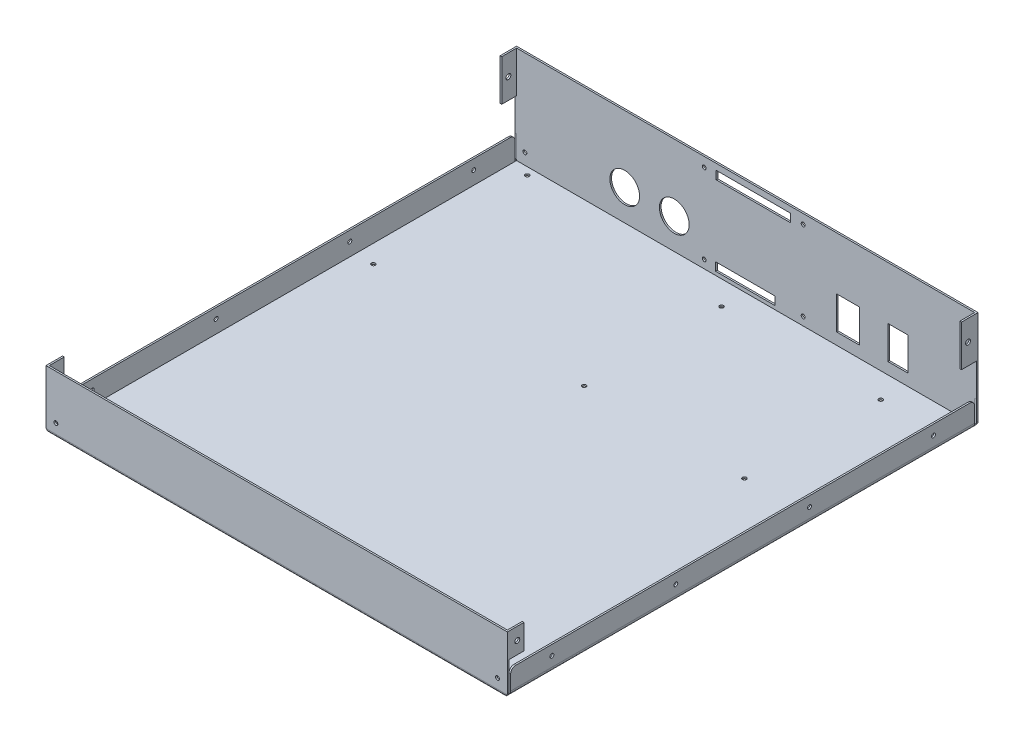
SolidWorks part; units mm, degrees
material "AISI 1015 Steel, Cold Drawn (SS)"
ref_plane "Front Plane" through (0, 0, 0) normal (0, 0, 1) x (1, 0, 0)
ref_plane "Top Plane" through (0, 0, 0) normal (0, 1, 0) x (1, 0, 0)
ref_plane "Right Plane" through (0, 0, 0) normal (1, 0, 0) x (0, 0, -1)
sketch "Sketch6" plane through (0, 0, 0) normal (0, 1, 0) x (1, 0, 0)
  line L1 (0, -162.3156) -> (279.4, -162.3156)
  line L2 (0, -162.3156) -> (0, 122.6844)
  line L3 (0, 122.6844) -> (279.4, 122.6844)
  line L4 (279.4, -162.3156) -> (279.4, 122.6844)
  dimension "D1" = 285
  dimension "D2" = 279.4
extrude "Boss-Extrude2" add sketch "Sketch6" along normal blind 60
sketch "Sketch8" plane through (0, 0, 0) normal (1, 0, 0) x (0, 0, -1)
  line L0 (-162.3156, 35) -> (-161.3156, 35)
  line L1 (-162.3156, 60) -> (-162.3156, 0) construction
  line L2 (-161.3156, 35) -> (-161.3156, 15)
  line L3 (-161.3156, 15) -> (121.6844, 15)
  line L4 (121.6844, 15) -> (121.6844, 60)
  line L5 (-162.3156, 60) -> (122.6844, 60) construction
  line L6 (121.6844, 60) -> (-162.3156, 60)
  line L7 (-162.3156, 60) -> (-162.3156, 35)
  line L8 (122.6844, 60) -> (122.6844, 0) construction
  line L9 (-162.3156, 0) -> (122.6844, 0) construction
  dimension "D1" = 1
  dimension "D2" = 1
  dimension "D3" = 15
  dimension "D4" = 35
extrude "Cut-Extrude7" cut sketch "Sketch8" against normal blind 60 and the other way through all from offset 30
shell "Shell1" thickness 1 removed face at (139.7, 15, 19.8156)
sketch "Sketch9" plane through (0, 0, -122.6844) normal (0, 0, -1) x (-1, 0, 0)
  line L0 (-279.4, 60) -> (0, 60) construction
  line L1 (-279.4, 60) -> (-279.4, 0) construction
  line L2 (-279.4, 0) -> (0, 0) construction
  line L3 (0, 60) -> (0, 0) construction
  line L4 (-279.4, 60) -> (0, 60)
  line L5 (-279.4, 60) -> (-279.4, 3)
  line L6 (-276.4, 0) -> (-3, 0)
  line L7 (0, 60) -> (0, 3)
  arc A0 (-276.4, 0) -> (-279.4, 3) centre (-276.4, 3) cw
  arc A1 (-3, 0) -> (0, 3) centre (-3, 3) ccw
  dimension "D1" = 3
extrude "Cut-Extrude8" cut sketch "Sketch9" against normal through all flip side to cut
sketch "Sketch11" plane through (279.4, 0, 0) normal (1, 0, 0) x (0, 0, -1)
  line L0 (-162.3156, 0) -> (122.6844, 0) construction
  line L1 (-161.3156, 15) -> (-157.3156, 15)
  line L2 (-161.3156, 15) -> (-161.3156, 1.9)
  line L3 (-160.4156, 1) -> (-160.3156, 1)
  line L4 (-160.3156, 12) -> (-160.3156, 1)
  line L6 (121.6836, 15.0003) -> (117.6836, 15.0003)
  line L7 (121.6836, 15.0003) -> (121.6836, 1.9)
  line L8 (120.7836, 1) -> (120.6836, 1)
  line L9 (120.6836, 12.0003) -> (120.6836, 1)
  arc A0 (120.7836, 1) -> (121.6836, 1.9) centre (120.7836, 1.9) ccw
  arc A1 (-161.3156, 1.9) -> (-160.4156, 1) centre (-160.4156, 1.9) ccw
  arc A2 (120.6836, 12.0003) -> (117.6836, 15.0003) centre (117.6836, 12.0003) ccw
  arc A3 (-160.3156, 12) -> (-157.3156, 15) centre (-157.3156, 12) cw
  dimension "D5" = 0.9
  dimension "D6" = 0.9
  dimension "D3" = 3
  dimension "D2" = 1
  dimension "D4" = 1
extrude "Cut-Extrude11" cut sketch "Sketch11" against normal through all
fillet "Fillet2" radius 2 2 edges at (139.7, 0, -122.6844) (139.7, 0, 162.3156) tangent propagation no
sketch "Sketch13" plane through (279.4, 0, 0) normal (1, 0, 0) x (0, 0, -1)
  line L0 (-157.3156, 15) -> (117.7237, 15) construction
  line L1 (-19.816, 3) -> (-19.816, 69.1905) construction
  line L2 (-160.3156, 3) -> (120.6836, 3) construction
  line L3 (-160.3156, 9) -> (141.1101, 9) construction
  line L4 (-160.3156, 3) -> (-160.3156, 12) construction
  circle A0 centre (-135.3156, 9) radius 1.5
  circle A1 centre (-60.3156, 9) radius 1.5
  circle A2 centre (20.6836, 9) radius 1.5
  circle A3 centre (95.6836, 9) radius 1.5
  dimension "D1" = 3
  dimension "D3" = 25
  dimension "D2" = 6
  dimension "D4" = 2
sketch "Sketch14" plane through (279.4, 0, 0) normal (1, 0, 0) x (0, 0, -1)
  line L0 (-162.3156, 35) -> (-162.3156, 3) construction
  line L1 (-162.3156, 35) -> (-152.3156, 35)
  line L2 (-162.3156, 35) -> (-162.3156, 20)
  line L3 (-162.3156, 20) -> (-152.3156, 20)
  line L4 (-152.3156, 35) -> (-152.3156, 20)
  line L5 (122.6844, 60) -> (112.6844, 60)
  line L6 (122.6844, 60) -> (122.6844, 35)
  line L7 (122.6844, 35) -> (112.6844, 35)
  line L8 (112.6844, 60) -> (112.6844, 35)
  line L9 (-162.3156, 35) -> (-161.3156, 35) construction
  dimension "D1" = 10
  dimension "D2" = 25
  dimension "D3" = 10
  dimension "D4" = 15
extrude "Boss-Extrude3" add sketch "Sketch14" against normal blind 1
sketch "Sketch15" plane through (0, 0, 0) normal (-1, 0, 0) x (0, 0, 1)
  line L1 (152.3156, 35) -> (162.3156, 35)
  line L2 (152.3156, 35) -> (152.3156, 20)
  line L3 (152.3156, 20) -> (162.3156, 20)
  line L4 (162.3156, 35) -> (162.3156, 20)
  line L5 (-112.6844, 60) -> (-122.6844, 60)
  line L6 (-112.6844, 60) -> (-112.6844, 35)
  line L7 (-112.6844, 35) -> (-122.6844, 35)
  line L8 (-122.6844, 60) -> (-122.6844, 35)
  dimension "D1" = 10
  dimension "D2" = 25
  dimension "D3" = 10
  dimension "D4" = 15
extrude "Boss-Extrude4" add sketch "Sketch15" against normal blind 1
sketch "Sketch16" plane through (0, 0, 0) normal (-1, 0, 0) x (0, 0, 1)
  line L0 (162.3156, 35) -> (162.3156, 3) construction
  line L1 (-122.6844, 60) -> (-122.6844, 3) construction
  circle A0 centre (156.3156, 27.5) radius 1.5
  circle A1 centre (-116.6844, 47.5) radius 1.5
  dimension "D1" = 6
  dimension "D2" = 6
extrude "Cut-Extrude14" cut sketch "Sketch16" against normal through all
hole_wizard "3/32 (0.09375) Diameter Hole2" positions "Sketch21" profile "Sketch20" hole size "3/32" standard "ANSI Inch"
sketch "Sketch21" plane through (0, 0, 162.3156) normal (0, 0, 1) x (1, 0, 0)
  point P0 (6, 7.825)
  point P3 (273.4, 7.825)
sketch "Sketch20" plane through (6, 7.825, 162.3156) normal (1, 0, 0) x (0, -1, 0)
  line L0 (0, 0) -> (0, 12.6554)
  line L1 (0, 12.6554) -> (1.1906, 11.94)
  line L2 (1.1906, 11.94) -> (1.1906, 0)
  line L5 (1.1906, 0) -> (0, 0)
  line L10 (0, 12.6554) -> (-1.1906, 11.94) construction
  line L11 (0, -6.35) -> (0, 107.95) construction
  dimension "Hole Dia." = 2.3812
  dimension "Hole Depth" = 11.94
  dimension "Drill Angle" = 118
hole_wizard "3/32 (0.09375) Diameter Hole3" positions "Sketch23" profile "Sketch22" hole size "3/32" standard "ANSI Inch"
sketch "Sketch23" plane through (0, 0, -122.6844) normal (0, 0, -1) x (-1, 0, 0)
  point P0 (-6, 7.825)
  point P3 (-273.4, 7.825)
sketch "Sketch22" plane through (6, 7.825, -122.6844) normal (1, 0, 0) x (0, 1, 0)
  line L0 (0, 0) -> (0, 12.6554)
  line L1 (0, 12.6554) -> (1.1906, 11.94)
  line L2 (1.1906, 11.94) -> (1.1906, 0)
  line L5 (1.1906, 0) -> (0, 0)
  line L10 (0, 12.6554) -> (-1.1906, 11.94) construction
  line L11 (0, -6.35) -> (0, 107.95) construction
  dimension "Hole Dia." = 2.3812
  dimension "Hole Depth" = 11.94
  dimension "Drill Angle" = 118
sketch "Sketch36" plane through (0, 0, -122.6844) normal (0, 0, -1) x (-1, 0, 0)
  line L0 (-279.4, 60) -> (-279.4, 3) construction
  line L1 (-194.6663, 8) -> (-208.6663, 8)
  line L2 (-194.6663, 8) -> (-194.6663, 28)
  line L3 (-194.6663, 28) -> (-208.6663, 28)
  line L4 (-208.6663, 8) -> (-208.6663, 28)
  line L5 (-279.2284, 2) -> (-0.1716, 2) construction
  line L6 (-237.9, 28) -> (-225.9, 28)
  line L7 (-237.9, 28) -> (-237.9, 8)
  line L8 (-237.9, 8) -> (-225.9, 8)
  line L9 (-225.9, 28) -> (-225.9, 8)
  line L11 (-166.8765, 51.3214) -> (-121.8765, 51.3214)
  line L12 (-166.8765, 51.3214) -> (-166.8765, 56.3214)
  line L13 (-166.8765, 56.3214) -> (-121.8765, 56.3214)
  line L14 (-121.8765, 51.3214) -> (-121.8765, 56.3214)
  line L15 (-166.8765, 51.3214) -> (-121.8765, 56.3214) construction
  line L16 (-166.8765, 56.3214) -> (-121.8765, 51.3214) construction
  line L17 (-157.5724, 3.1942) -> (-121.5724, 3.1942)
  line L18 (-157.5724, 3.1942) -> (-157.5724, 8.1942)
  line L19 (-157.5724, 8.1942) -> (-121.5724, 8.1942)
  line L20 (-121.5724, 3.1942) -> (-121.5724, 8.1942)
  line L21 (-157.5724, 3.1942) -> (-121.5724, 8.1942) construction
  line L22 (-157.5724, 8.1942) -> (-121.5724, 3.1942) construction
  circle A0 centre (-96.4719, 19.6) radius 9
  circle A1 centre (-66.4719, 19.6) radius 9
  point P12 (-144.3765, 53.8214)
  point P17 (-139.5724, 5.6942)
  dimension "D13" = 18
  dimension "D14" = 18
  dimension "D1" = 14
  dimension "D2" = 20
  dimension "D3" = 12
  dimension "D4" = 20
  dimension "D5" = 6
  dimension "D6" = 6
  dimension "D7" = 17.2337
  dimension "D8" = 41.5
  dimension "D9" = 5
  dimension "D10" = 5
  dimension "D11" = 45
  dimension "D12" = 36
extrude "Cut-Extrude15" cut sketch "Sketch36" against normal blind 2
hole_wizard "3/32 (0.09375) Diameter Hole5" positions "Sketch38" profile "Sketch37" hole size "3/32" standard "ANSI Inch" end condition through all
sketch "Sketch38" plane through (279.4, 0, 0) normal (1, 0, 0) x (0, 0, -1)
  point P0 (-135.3156, 9)
  point P3 (-60.3156, 9)
  point P6 (20.6836, 9)
  point P9 (95.6836, 9)
sketch "Sketch37" plane through (279.4, 9, 135.3156) normal (0, 1, 0) x (0, 0, -1)
  line L0 (0, 0) -> (0, 279.4)
  line L1 (0, 279.4) -> (1.1906, 279.4)
  line L2 (1.1906, 279.4) -> (1.1906, 0)
  line L5 (1.1906, 0) -> (0, 0)
  line L11 (0, -6.35) -> (0, 107.95) construction
  dimension "Thru Hole Dia." = 2.3812
  dimension "Thru Hole Depth" = 279.4
hole_wizard "3/32 (0.09375) Diameter Hole8" positions "Sketch44" profile "Sketch43" hole size "3/32" standard "ANSI Inch"
sketch "Sketch44" plane through (0, 0, 0) normal (0, -1, 0) x (-1, 0, 0)
  point P0 (-11.9691, 117.1444)
  point P3 (-139.6346, 107.1444)
  point P6 (-236.6716, 106.5227)
  point P9 (-236.6716, 23.9727)
  point P12 (-139.6346, 23.9727)
  point P15 (-11.9691, 23.9727)
sketch "Sketch43" plane through (11.9691, 0, -117.1444) normal (1, 0, 0) x (0, 0, -1)
  line L0 (0, 0) -> (0, 2.7154)
  line L1 (0, 2.7154) -> (1.1906, 2)
  line L2 (1.1906, 2) -> (1.1906, 0)
  line L5 (1.1906, 0) -> (0, 0)
  line L10 (0, 2.7154) -> (-1.1906, 2) construction
  line L11 (0, -6.35) -> (0, 107.95) construction
  dimension "Hole Dia." = 2.3812
  dimension "Hole Depth" = 2
  dimension "Drill Angle" = 118
hole_wizard "3/32 (0.09375) Diameter Hole9" positions "Sketch49" profile "Sketch48" hole size "3/32" standard "ANSI Inch"
sketch "Sketch49" plane through (0, 0, -122.6844) normal (0, 0, -1) x (-1, 0, 0)
  point P0 (-174.5265, 6.0037)
  point P3 (-114.6065, 6.0037)
  point P6 (-114.6065, 54.2637)
  point P9 (-174.5265, 54.2637)
sketch "Sketch48" plane through (174.5265, 6.0037, -122.6844) normal (1, 0, 0) x (0, 1, 0)
  line L0 (0, 0) -> (0, 2.7154)
  line L1 (0, 2.7154) -> (1.1906, 2)
  line L2 (1.1906, 2) -> (1.1906, 0)
  line L5 (1.1906, 0) -> (0, 0)
  line L10 (0, 2.7154) -> (-1.1906, 2) construction
  line L11 (0, -6.35) -> (0, 107.95) construction
  dimension "Hole Dia." = 2.3812
  dimension "Hole Depth" = 2
  dimension "Drill Angle" = 118
